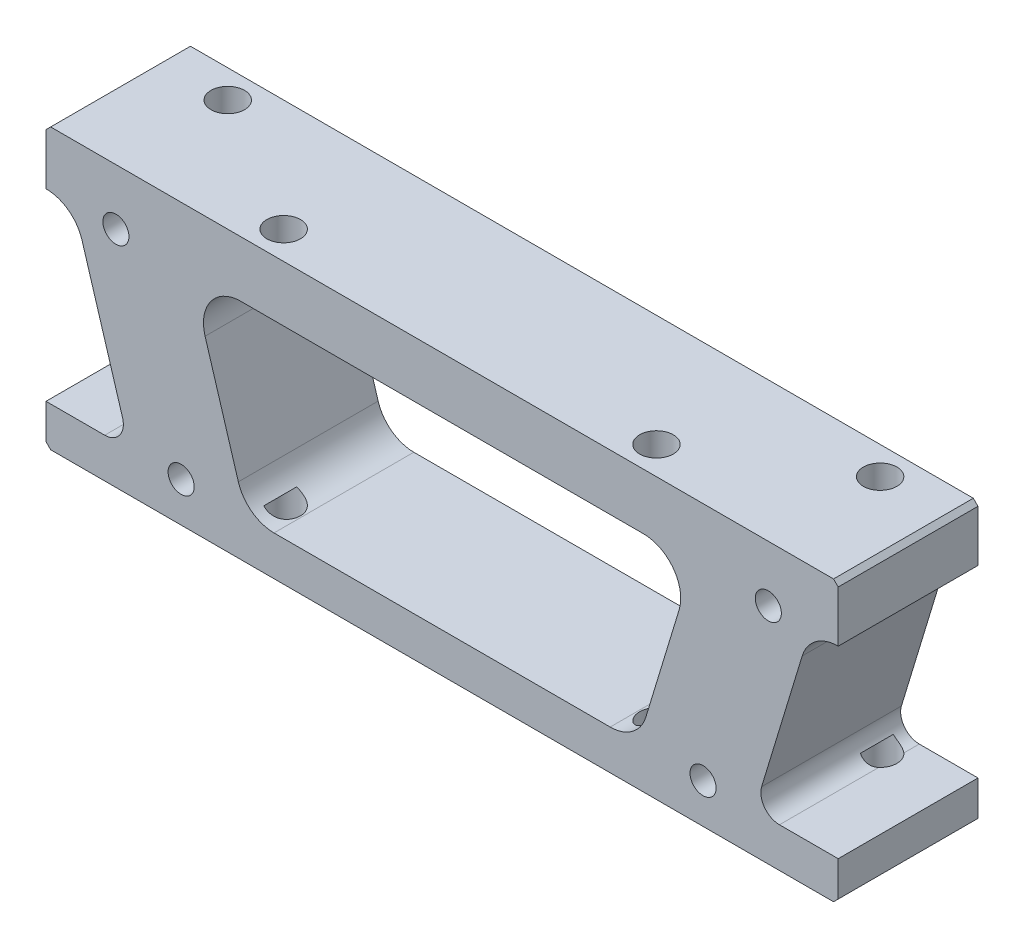
SolidWorks part; units mm, degrees
ref_plane "前视基准面" through (0, 0, 0) normal (0, 0, 1) x (1, 0, 0)
ref_plane "上视基准面" through (0, 0, 0) normal (0, 1, 0) x (1, 0, 0)
ref_plane "右视基准面" through (0, 0, 0) normal (1, 0, 0) x (0, 0, -1)
sketch "草图1" plane through (0, 0, 0) normal (0, 1, 0) x (1, 0, 0)
  line L1 (-42.5, 7.5) -> (42.5, 7.5)
  line L2 (-42.5, 7.5) -> (-42.5, -7.5)
  line L3 (-42.5, -7.5) -> (42.5, -7.5)
  line L4 (42.5, 7.5) -> (42.5, -7.5)
  line L5 (-42.5, 7.5) -> (42.5, -7.5) construction
  line L6 (-42.5, -7.5) -> (42.5, 7.5) construction
  dimension "D1" = 85
  dimension "D2" = 15
extrude "凸台-拉伸1" add sketch "草图1" along normal blind 30
sketch "草图2" plane through (0, 0, 7.5) normal (0, 0, 1) x (1, 0, 0)
  line L0 (0, 30) -> (0, 24) construction
  line L1 (0, 24) -> (-35, 24) construction
  line L2 (0, 24) -> (35, 24) construction
  line L3 (0, 24) -> (0, 4) construction
  line L4 (0, 4) -> (28, 4.2557) construction
  line L5 (0, 4) -> (-28, 4.2557) construction
  line L6 (0, 30) -> (0, 37.6117) construction
  line L7 (-42.5, 30) -> (42.5, 30) construction
  circle A0 centre (-35, 24) radius 1.4
  circle A1 centre (35, 24) radius 1.4
  circle A2 centre (28, 4.2557) radius 1.4
  circle A3 centre (-28, 4.2557) radius 1.4
extrude "切除-拉伸1" cut sketch "草图2" against normal blind 40
sketch "草图3" plane through (0, 0, 7.5) normal (0, 0, 1) x (1, 0, 0)
  line L0 (-27, 24) -> (27, 24)
  line L1 (-27, 24) -> (-21, 4.2557)
  line L2 (-21, 4.2557) -> (21, 4.2557)
  line L3 (0, 0) -> (0, 30) construction
  line L4 (-42.5, 30) -> (42.5, 30) construction
  line L5 (27, 24) -> (21, 4.2557)
  point P12 (0, 4.2557)
  point P13 (0, 24)
extrude "切除-拉伸2" cut sketch "草图3" against normal blind 40
fillet "圆角1" radius 4 4 edges at (-27, 24, 0) (27, 24, 0) (21, 4.2557, 0) (-21, 4.2557, 0)
sketch "草图5" plane through (0, 30, 0) normal (0, 1, 0) x (1, 0, 0)
  line L0 (-20, -4.5) -> (20, -4.5) construction
  line L1 (0, 4.5) -> (0, -4.5) construction
  line L2 (-35, 4.5) -> (0, 4.5) construction
  line L3 (0, 4.5) -> (35, 4.5) construction
  line L4 (0, 7.5) -> (0, 4.5) construction
  circle A0 centre (-35, 4.5) radius 1.8
  circle A1 centre (35, 4.5) radius 1.8
  circle A2 centre (-20, -4.5) radius 1.8
  circle A3 centre (20, -4.5) radius 1.8
  point P0 (0, 0)
extrude "切除-拉伸3" cut sketch "草图5" against normal blind 5
ref_plane "基准面1" through (0, 15, 0) normal (0, 1, 0) x (1, 0, 0)
chamfer "倒角1" distance 0.5 angle 45 4 edges at (-42.5, 0, 0) (42.5, 0, 0) (42.5, 30, 0) (-42.5, 30, 0)
sketch "草图6" plane through (0, 0, 7.5) normal (0, 0, 1) x (1, 0, 0)
  line L0 (-42.5, 24) -> (-39.5, 24)
  line L1 (-42.5, 29.5) -> (-42.5, 0.5) construction
  line L2 (-39.5, 24) -> (-33.5, 4.2557)
  line L3 (-33.5, 4.2557) -> (-42.5, 4.2557)
  line L4 (-25.431, 18.837) -> (-21.8621, 7.0927) construction
  line L5 (-25.431, 18.837) -> (-21.8621, 7.0927) construction
  line L6 (0, 30) -> (0, 0) construction
  line L7 (-42, 30) -> (42, 30) construction
  line L8 (-42.5, 24) -> (-42.5, 4.2557)
  line L9 (42.5, 24) -> (42.5, 4.2557)
  line L10 (33.5, 4.2557) -> (42.5, 4.2557)
  line L11 (39.5, 24) -> (33.5, 4.2557)
  line L12 (42.5, 24) -> (39.5, 24)
extrude "切除-拉伸4" cut sketch "草图6" against normal blind 24
fillet "圆角3" radius 4 2 edges at (39.5, 24, 0) (-39.5, 24, 0)
sketch "草图9" plane through (0, 0, 0) normal (0, -1, 0) x (1, 0, 0)
  circle A0 centre (20, 4.5) radius 1.8 construction
  circle A1 centre (-20, 4.5) radius 1.8 construction
  circle A2 centre (-35, -4.5) radius 1.8 construction
  circle A3 centre (35, -4.5) radius 1.8 construction
  circle A4 centre (20, 4.5) radius 1.8
  circle A5 centre (-20, 4.5) radius 1.8
  circle A6 centre (-35, -4.5) radius 1.8
  circle A7 centre (35, -4.5) radius 1.8
extrude "切除-拉伸5" cut sketch "草图9" against normal blind 5
fillet "圆角4" radius 2 2 edges at (-33.5, 4.2557, 1.9975) (33.5, 4.2557, 1.9975)
